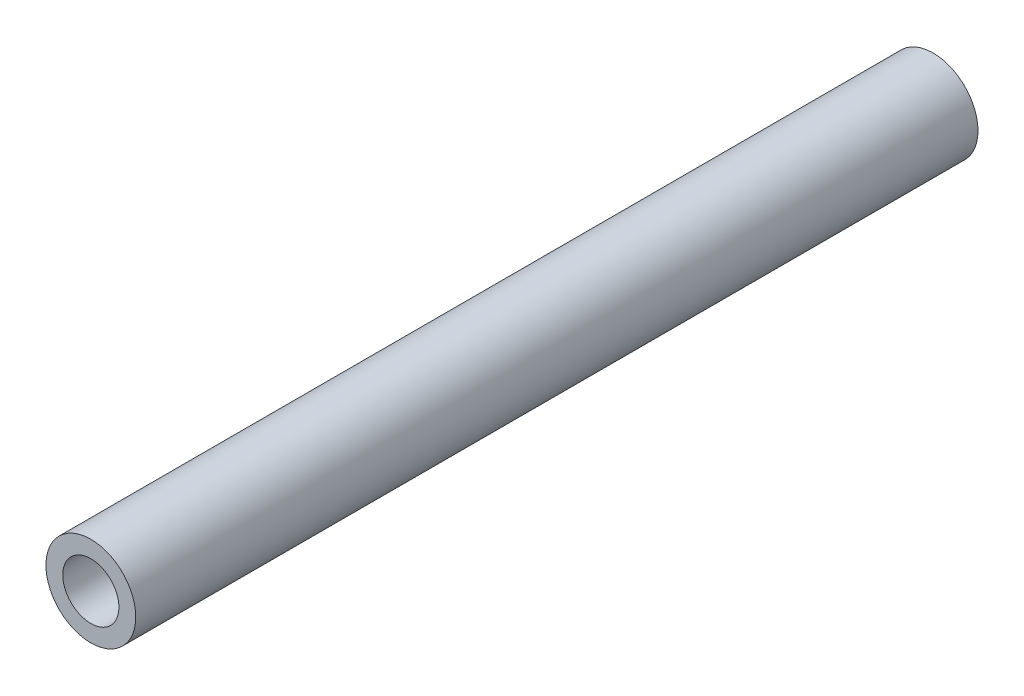
SolidWorks part; units mm, degrees
ref_plane "Front Plane" through (0, 0, 0) normal (0, 0, 1) x (1, 0, 0)
ref_plane "Top Plane" through (0, 0, 0) normal (0, 1, 0) x (1, 0, 0)
ref_plane "Right Plane" through (0, 0, 0) normal (1, 0, 0) x (0, 0, -1)
sketch "Sketch1" plane through (0, 0, 0) normal (0, 0, 1) x (1, 0, 0)
  circle A0 centre (0, 0) radius 16
  circle A1 centre (0, 0) radius 10
  dimension "D1" = 32
  dimension "D2" = 20
extrude "Boss-Extrude1" add sketch "Sketch1" along normal blind 300
